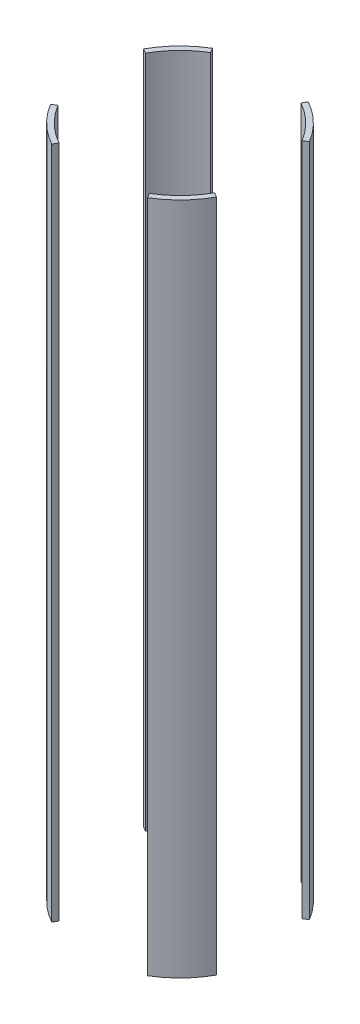
SolidWorks part; units mm, degrees
ref_plane "Front Plane" through (0, 0, 0) normal (0, 0, 1) x (1, 0, 0)
ref_plane "Top Plane" through (0, 0, 0) normal (0, 1, 0) x (1, 0, 0)
ref_plane "Right Plane" through (0, 0, 0) normal (1, 0, 0) x (0, 0, -1)
sketch "Sketch2" plane through (0, 0, 0) normal (0, 1, 0) x (1, 0, 0)
  circle A0 centre (0, 0) radius 88.9
  circle A1 centre (0, 0) radius 83.82
  dimension "D1" = 177.8
  dimension "D2" = 167.64
extrude "Boss-Extrude1" add sketch "Sketch2" along normal mid plane 635
sketch "Sketch3" plane through (0, 0, 0) normal (0, 1, 0) x (1, 0, 0)
  line L0 (0, 0) -> (169.6618, 101.6776)
  line L1 (-58.1167, 96.9749) -> (0, 0)
  line L2 (0, 0) -> (53.9, 96.9749)
  line L3 (53.9, 96.9749) -> (-58.1167, 96.9749)
  line L4 (0, 0) -> (70.9917, -118.4586)
  line L5 (70.9917, -118.4586) -> (-65.8409, -118.4586)
  line L6 (-65.8409, -118.4586) -> (0, 0)
  line L7 (169.6618, 101.6776) -> (169.6618, -94.3004)
  line L8 (169.6618, -94.3004) -> (0, 0)
  line L9 (0, 0) -> (-123.7413, 68.7771)
  line L10 (-123.7413, 68.7771) -> (-123.7413, -74.1577)
  line L11 (-123.7413, -74.1577) -> (0, 0)
  dimension "D1" = 60
  dimension "D2" = 60
  dimension "D3" = 60
  dimension "D4" = 60
  dimension "D5" = 30
  dimension "D6" = 30
extrude "Cut-Extrude1" cut sketch "Sketch3" against normal through all both and the other way through all contours L8 L7 L0 | L2 L3 L1 | L10 L11 L9 | L6 L5 L4 region at (-1.4056, 0, -64.65) region at (1.7169, 0, 78.9724) region at (113.1078, 0, -2.4591) region at (-82.4942, 0, 1.7935)
equation "\"D1@Boss-Extrude1\"=3*12"
